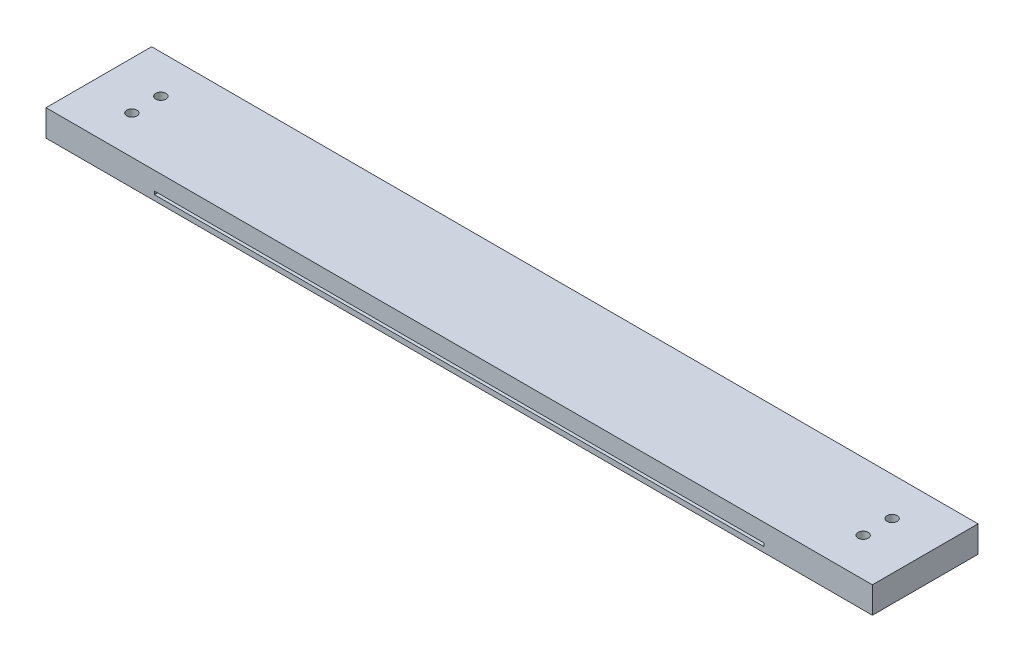
SolidWorks part; units mm, degrees
ref_plane "Front Plane" through (0, 0, 0) normal (0, 0, 1) x (1, 0, 0)
ref_plane "Top Plane" through (0, 0, 0) normal (0, 1, 0) x (1, 0, 0)
ref_plane "Right Plane" through (0, 0, 0) normal (1, 0, 0) x (0, 0, -1)
sketch "Sketch1" plane through (0, 0, 0) normal (1, 0, 0) x (0, 0, -1)
  line L1 (0, 0) -> (40, 0)
  line L2 (0, 0) -> (0, 10)
  line L3 (0, 10) -> (40, 10)
  line L4 (40, 0) -> (40, 10)
  dimension "D1" = 10
  dimension "D2" = 40
extrude "Boss-Extrude1" add sketch "Sketch1" along normal blind 312.998
sketch "Sketch2" plane through (0, 0, -40) normal (0, 0, -1) x (-1, 0, 0)
  line L1 (-271.949, 2) -> (-41.049, 2)
  line L2 (-271.949, 2) -> (-271.949, 3.2)
  line L3 (-271.949, 3.2) -> (-41.049, 3.2)
  line L4 (-41.049, 2) -> (-41.049, 3.2)
  line L5 (-271.949, 3.2) -> (-312.998, 0) construction
  line L6 (-41.049, 3.2) -> (0, 0) construction
  line L7 (-312.998, 0) -> (0, 0) construction
  dimension "D1" = 230.9
  dimension "D2" = 2
  dimension "D3" = 1.2
extrude "Cut-Extrude1" cut sketch "Sketch2" against normal through all
sketch "Sketch3" plane through (0, 10, 0) normal (0, 1, 0) x (1, 0, 0)
  line L0 (156.499, 71.4665) -> (156.499, -49.9307) construction
  line L1 (0, 40) -> (156.499, 71.4665) construction
  line L2 (156.499, 71.4665) -> (312.998, 40) construction
  line L3 (312.998, 40) -> (312.998, 0) construction
  line L4 (312.998, 40) -> (0, 40) construction
  line L5 (312.998, 40) -> (294.998, 25.5) construction
  line L6 (294.998, 25.5) -> (294.998, 14.5) construction
  line L7 (294.998, 14.5) -> (312.998, 0) construction
  circle A0 centre (294.998, 25.5) radius 1.9177
  circle A1 centre (294.998, 14.5) radius 1.9177
  circle A2 centre (18, 14.5) radius 1.9177
  circle A3 centre (18, 25.5) radius 1.9177
  dimension "D3" = 3.8354
  dimension "D1" = 18
  dimension "D2" = 14.5
extrude "Cut-Extrude2" cut sketch "Sketch3" against normal through all
sketch "Sketch4" plane through (0, 0, 0) normal (0, -1, 0) x (1, 0, 0)
  line L1 (14.5837, -12.5276) -> (14.5837, -16.4724)
  line L2 (14.5837, -16.4724) -> (18, -18.4448)
  line L3 (18, -18.4448) -> (21.4163, -16.4724)
  line L4 (21.4163, -16.4724) -> (21.4163, -12.5276)
  line L5 (21.4163, -12.5276) -> (18, -10.5552)
  line L6 (18, -10.5552) -> (14.5837, -12.5276)
  line L7 (14.5837, -23.5276) -> (14.5837, -27.4724)
  line L8 (14.5837, -27.4724) -> (18, -29.4448)
  line L9 (18, -29.4448) -> (21.4163, -27.4724)
  line L10 (21.4163, -27.4724) -> (21.4163, -23.5276)
  line L11 (21.4163, -23.5276) -> (18, -21.5552)
  line L12 (18, -21.5552) -> (14.5837, -23.5276)
  line L13 (298.4143, -12.5276) -> (294.998, -10.5552)
  line L14 (294.998, -10.5552) -> (291.5817, -12.5276)
  line L15 (291.5817, -12.5276) -> (291.5817, -16.4724)
  line L16 (291.5817, -16.4724) -> (294.998, -18.4448)
  line L17 (294.998, -18.4448) -> (298.4143, -16.4724)
  line L18 (298.4143, -16.4724) -> (298.4143, -12.5276)
  line L19 (291.5817, -23.5276) -> (291.5817, -27.4724)
  line L20 (291.5817, -27.4724) -> (294.998, -29.4448)
  line L21 (294.998, -29.4448) -> (298.4143, -27.4724)
  line L22 (298.4143, -27.4724) -> (298.4143, -23.5276)
  line L23 (298.4143, -23.5276) -> (294.998, -21.5552)
  line L24 (294.998, -21.5552) -> (291.5817, -23.5276)
  circle A0 centre (18, -14.5) radius 3.4163 construction
  circle A1 centre (18, -25.5) radius 3.4163 construction
  circle A2 centre (294.998, -14.5) radius 3.4163 construction
  circle A3 centre (294.998, -25.5) radius 3.4163 construction
  dimension "D1" = 6.8326
extrude "Cut-Extrude3" cut sketch "Sketch4" against normal blind 4.3
